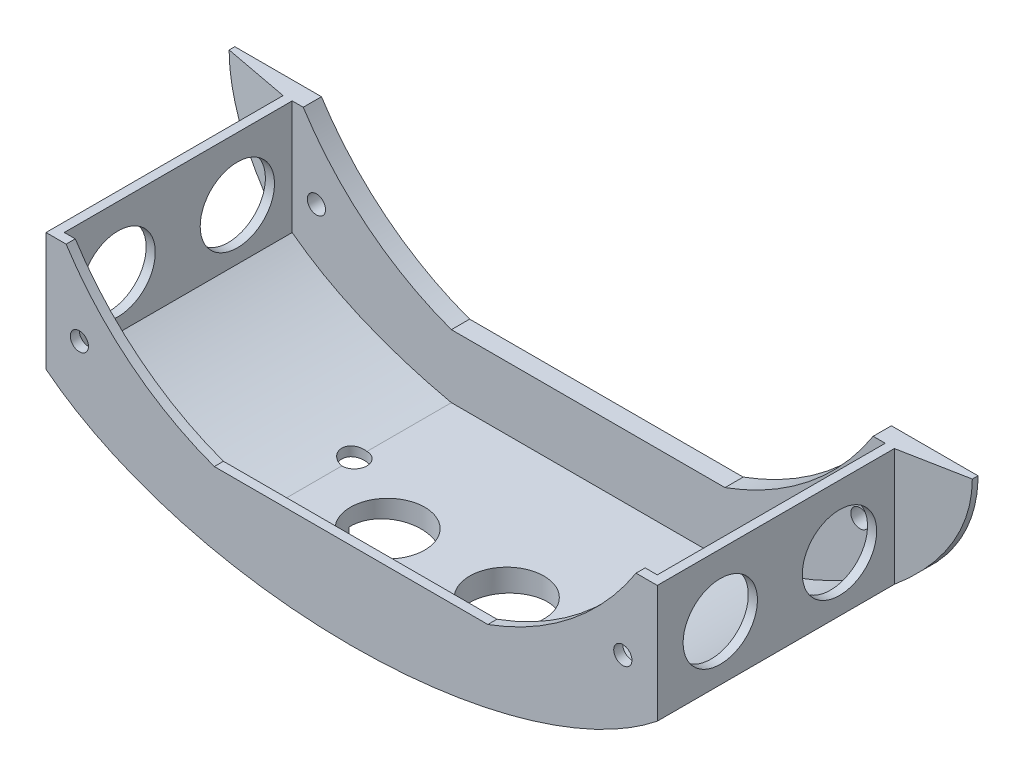
SolidWorks part; units mm, degrees
ref_plane "Alzado" through (0, 0, 0) normal (0, 0, 1) x (1, 0, 0)
ref_plane "Planta" through (0, 0, 0) normal (0, 1, 0) x (1, 0, 0)
ref_plane "Vista lateral" through (0, 0, 0) normal (1, 0, 0) x (0, 0, -1)
sketch "Croquis1" plane through (0, 0, 0) normal (0, 0, 1) x (1, 0, 0)
  line L0 (0, 14) -> (30, 14)
  line L1 (-76.5, 40) -> (-62.5, 40)
  line L2 (0, 14) -> (-30, 14)
  line L3 (0, 0) -> (0, 40) construction
  line L4 (62.5, 40) -> (76.5, 40)
  line L5 (-59.6, 23) -> (59.6, 23) construction
  line L6 (-7.25, 8) -> (7.25, 8) construction
  line L7 (81.5, 40) -> (76.5, 40)
  line L8 (-81.5, 40) -> (-76.5, 40)
  circle A1 centre (59.6, 23) radius 2
  circle A3 centre (-59.6, 23) radius 2
  arc A4 (-30, 14) -> (-62.5, 40) centre (-7.7821, 75.0849) cw
  arc A5 (30, 14) -> (62.5, 40) centre (7.7821, 75.0849) ccw
  ellipse E0 centre (0, 40) end of major axis (76.5, 40) minor radius 40 (-76.5, 40) -> (76.5, 40) ccw
  spline S0 degree 1 poles (-81.5, 40) (81.5, 40) knots 0 0 1 1 construction
  spline S1 degree 3 poles (-81.5, 40) (-81.5, 36.7505) (-80.261, 30.281) (-73.3217, 18.4428) (-57.7398, 6.4288) (-31.0655, -2.8514) (0, -6.0743) (31.0655, -2.8514) (57.7398, 6.4288) (73.3217, 18.4428) (80.261, 30.281) (81.5, 36.7505) (81.5, 40) knots 3.141593 3.141593 3.141593 3.141593 3.337942 3.534292 3.926991 4.31969 4.712389 5.105088 5.497787 5.890486 6.086836 6.283185 6.283185 6.283185 6.283185
  dimension "D3" = 65
  dimension "D4" = 4
  dimension "D1" = 153
  dimension "D2" = 30
  dimension "D5" = 40
  dimension "D6" = 14
  dimension "D7" = 14
  dimension "D8" = 119.2
  dimension "D9" = 15
  dimension "D10" = 8
  dimension "D11" = 14.5
  dimension "D12" = 5
extrude "Saliente-Extruir1" add sketch "Croquis1" along normal blind 4 contours L1 E0 L4 A5 L0 L2 A4 A1 A3 | L8 S1 L7 E0 region at (15, 12.4186, 0) region at (79, 38.309, 0)
sketch "Croquis3" plane through (0, 0, 4) normal (0, 0, 1) x (1, 0, 0)
  line L2 (-64.9152, 40) -> (-64.9152, 12.5008)
  line L4 (-81.5, 40) -> (-62.5, 40) construction
  line L6 (65.1546, 40) -> (65.1546, 12.6747)
  line L7 (62.5, 40) -> (81.5, 40) construction
  spline S1 degree 3 poles (1542.7355, -1097.7912) (170.097, 250.4745) (-119.0873, 96.5177) (-73.3217, 18.4428) (-57.7398, 6.4288) (-31.0655, -2.8514) (0, -6.0743) (31.0655, -2.8514) (57.7398, 6.4288) (73.3217, 18.4428) (119.0876, 96.5183) (-170.1018, 250.4771) (-1542.7713, -1097.8263) knots -1.252843 -1.252843 -1.252843 -1.252843 3.337942 3.534292 3.926991 4.31969 4.712389 5.105088 5.497787 5.890486 6.086836 10.67766 10.67766 10.67766 10.67766 only from (-81.5, 40) to (81.5, 40) construction
  spline S2 degree 3 poles (-81.5, 40) (-81.5, 36.7505) (-80.261, 30.281) (-73.3217, 18.4428) (-57.7398, 6.4288) (-31.0655, -2.8514) (0, -6.0743) (31.0655, -2.8514) (57.7398, 6.4288) (73.3217, 18.4428) (80.261, 30.281) (81.5, 36.7505) (81.5, 40) knots 3.141593 3.141593 3.141593 3.141593 3.337942 3.534292 3.926991 4.31969 4.712389 5.105088 5.497787 5.890486 6.086836 6.283185 6.283185 6.283185 6.283185
  spline S3 degree 1 poles (-79.5, 40) (79.5, 40) knots 0 0 1 1 construction
  spline S4 degree 3 poles (-79.5, 40) (-79.5, 36.9913) (-78.3621, 31.0317) (-73.4854, 22.677) (-65.8626, 15.2348) (-52.4779, 6.7299) (-30.655, -0.8785) (0, -4.0608) (30.655, -0.8785) (52.4779, 6.7299) (65.8626, 15.2348) (73.4854, 22.677) (78.3621, 31.0317) (79.5, 36.9913) (79.5, 40) knots 3.141593 3.141593 3.141593 3.141593 3.337942 3.534292 3.730641 3.926991 4.31969 4.712389 5.105088 5.497787 5.694137 5.890486 6.086836 6.283185 6.283185 6.283185 6.283185
  point P13 (62.5, 40)
  point P14 (64.5, 18.4921)
  point P25 (-66.5, 18.4921)
  point P29 (66.5, 18.4921)
  dimension "D1" = 2
extrude "Saliente-Extruir4" add sketch "Croquis3" along normal blind 50 contours S4 L2 S2 L6 region at (0.1522, -4.3162, 4)
sketch "Croquis4" plane through (0, 0, 4) normal (0, 0, 1) x (1, 0, 0)
  line L0 (-64.9152, 12.5008) -> (-64.9152, 40)
  line L1 (65.1546, 12.6747) -> (65.1546, 40)
  line L2 (62.5, 40) -> (65.1546, 40)
  line L3 (-81.5, 40) -> (-62.5, 40) construction
  line L4 (62.5, 40) -> (81.5, 40) construction
  line L5 (-64.9152, 14.9913) -> (-64.9152, 12.5008) construction
  line L6 (65.1546, 40) -> (67.1546, 40)
  line L7 (-62.5, 40) -> (-64.9152, 40)
  line L8 (67.1546, 40) -> (67.1546, 14.2025)
  line L9 (-64.9152, 40) -> (-66.9152, 40)
  line L10 (-66.9152, 40) -> (-66.9152, 14.0121)
  spline S0 degree 3 poles (2914.6022, -7.6993) (68.4607, 352.6912) (-191.4209, 55.1717) (-30.655, -0.8785) (0, -4.0608) (30.655, -0.8785) (191.4186, 55.1709) (-68.4528, 352.6821) (-2914.4643, -7.6818) knots -2.519994 -2.519994 -2.519994 -2.519994 3.926991 4.31969 4.712389 5.105088 5.497787 11.944668 11.944668 11.944668 11.944668 only from (-64.9152, 14.9913) to (65.1546, 15.1748) construction
  spline S1 degree 3 poles (-64.9152, 14.9913) (-62.1057, 12.8492) (-52.2108, 6.6368) (-30.655, -0.8785) (0, -4.0608) (30.655, -0.8785) (52.3277, 6.6776) (62.2857, 12.9624) (65.1546, 15.1748) knots 3.742654 3.742654 3.742654 3.742654 3.926991 4.31969 4.712389 5.105088 5.497787 5.687379 5.687379 5.687379 5.687379
  spline S2 degree 3 poles (2240.248, -1814.2238) (260.5568, 296.6585) (-125.1968, 106.9404) (-2.0113, -103.2111) (970.3665, 127.2722) (-2357.6152, 1836.2842) knots -1.944329 -1.944329 -1.944329 -1.944329 3.337942 3.534292 11.998045 11.998045 11.998045 11.998045 only from (-81.5, 40) to (-64.9152, 12.5008) construction
  spline S3 degree 3 poles (2357.9097, 1836.4354) (-970.4226, 127.2855) (2.0091, -103.2149) (125.1968, 106.9403) (-260.5566, 296.6583) (-2240.2462, -1814.2218) knots -2.573517 -2.573517 -2.573517 -2.573517 5.890486 6.086836 11.369105 11.369105 11.369105 11.369105 only from (65.1546, 12.6747) to (81.5, 40) construction
  spline S4 degree 3 poles (-81.5, 40) (-81.5, 36.7505) (-80.261, 30.281) (-74.7278, 20.8415) (-68.7218, 15.2513) (-64.9152, 12.5008) knots 3.141593 3.141593 3.141593 3.141593 3.337942 3.534292 3.767846 3.767846 3.767846 3.767846
  spline S5 degree 3 poles (65.1546, 12.6747) (68.8587, 15.3792) (74.7712, 20.9156) (80.261, 30.281) (81.5, 36.7505) (81.5, 40) knots 5.661843 5.661843 5.661843 5.661843 5.890486 6.086836 6.283185 6.283185 6.283185 6.283185
  line M39 (65.1546, 15.1748) -> (65.1546, 12.6747)
  spline M40 degree 3 poles (-81.5, 40) (-81.5, 36.7505) (-80.261, 30.281) (-73.3217, 18.4428) (-57.7398, 6.4288) (-31.0655, -2.8514) (0, -6.0743) (31.0655, -2.8514) (57.7398, 6.4288) (73.3217, 18.4428) (80.261, 30.281) (81.5, 36.7505) (81.5, 40) knots 3.141593 3.141593 3.141593 3.141593 3.337942 3.534292 3.926991 4.31969 4.712389 5.105088 5.497787 5.890486 6.086836 6.283185 6.283185 6.283185 6.283185 only from (65.1546, 12.6747) to (81.5, 40)
  line M41 (81.5, 40) -> (62.5, 40)
  line M45 (-62.5, 40) -> (-81.5, 40)
  spline M46 degree 3 poles (-81.5, 40) (-81.5, 36.7505) (-80.261, 30.281) (-73.3217, 18.4428) (-57.7398, 6.4288) (-31.0655, -2.8514) (0, -6.0743) (31.0655, -2.8514) (57.7398, 6.4288) (73.3217, 18.4428) (80.261, 30.281) (81.5, 36.7505) (81.5, 40) knots 3.141593 3.141593 3.141593 3.141593 3.337942 3.534292 3.926991 4.31969 4.712389 5.105088 5.497787 5.890486 6.086836 6.283185 6.283185 6.283185 6.283185 only from (-81.5, 40) to (-64.9152, 12.5008)
  line M47 (-64.9152, 12.5008) -> (-64.9152, 14.9913)
  dimension "D1" = 2
  dimension "D2" = 2
extrude "Saliente-Extruir5" add sketch "Croquis4" along normal blind 50 contours L8 L1 M41 M39 M40 | L10 L0 M45 M46 M47 region at (-65.9058, 26.619, 4) region at (66.145, 26.7099, 4)
ref_plane "Plano1" through (0, 40, 0) normal (0, 1, 0) x (1, 0, 0)
sketch "Croquis6" plane through (0, 0, 4) normal (0, 0, 1) x (1, 0, 0)
  line L0 (-30, 0.1323) -> (30, 0.1323)
  line L2 (-30, 14) -> (30, 14) construction
  spline S1 degree 3 poles (923.1346, 169.1134) (-49.932, 196.9469) (-146.0678, 39.3595) (-30.655, -0.8785) (0, -4.0608) (30.655, -0.8785) (146.0605, 39.357) (49.9451, 196.9254) (-922.918, 169.1196) knots -0.479691 -0.479691 -0.479691 -0.479691 3.926991 4.31969 4.712389 5.105088 5.497787 9.904142 9.904142 9.904142 9.904142 only from (-64.9152, 14.9913) to (65.1546, 15.1748) construction
  spline S2 degree 3 poles (-64.9152, 14.9913) (-62.1057, 12.8492) (-52.2108, 6.6368) (-30.655, -0.8785) (0, -4.0608) (30.655, -0.8785) (52.3277, 6.6776) (62.2857, 12.9624) (65.1546, 15.1748) knots 3.742654 3.742654 3.742654 3.742654 3.926991 4.31969 4.712389 5.105088 5.497787 5.687379 5.687379 5.687379 5.687379
  spline M21 degree 3 poles (-79.5, 40) (-79.5, 36.9913) (-78.3621, 31.0317) (-73.4854, 22.677) (-65.8626, 15.2348) (-52.4779, 6.7299) (-30.655, -0.8785) (0, -4.0608) (30.655, -0.8785) (52.4779, 6.7299) (65.8626, 15.2348) (73.4854, 22.677) (78.3621, 31.0317) (79.5, 36.9913) (79.5, 40) knots 3.141593 3.141593 3.141593 3.141593 3.337942 3.534292 3.730641 3.926991 4.31969 4.712389 5.105088 5.497787 5.694137 5.890486 6.086836 6.283185 6.283185 6.283185 6.283185 only from (-64.9152, 14.9913) to (65.1546, 15.1748)
extrude "Saliente-Extruir6" add sketch "Croquis6" along normal blind 50 contours L0 M21 region at (0, -1.1242, 4)
sketch "Croquis5" plane through (0, 40, 0) normal (0, 1, 0) x (-1, 0, 0)
  line L0 (-30, 25.2801) -> (30, 25.2801) construction
  line L2 (-13.075, 34.9209) -> (13.075, 34.9209) construction
  line L3 (0, 34.9209) -> (0, 25.2801) construction
  circle A0 centre (-13.075, 34.9209) radius 8.15
  circle A1 centre (13.075, 34.9209) radius 8.15
  circle A4 centre (-30, 25.2801) radius 2.75
  circle A5 centre (30, 25.2801) radius 2.75
  point P9 (0, 34.9209)
  dimension "D1" = 16.3
  dimension "D6" = 5.5
  dimension "D2" = 26.15
  dimension "D5" = 60
extrude "Cortar-Extruir1" cut sketch "Croquis5" against normal through all
sketch "Croquis7" plane through (-66.9152, 0, 0) normal (-1, 0, 0) x (0, 0, 1)
  line L0 (54, 26.2504) -> (4, 26.2504) construction
  circle A0 centre (42.1812, 26.2504) radius 8.15
  circle A1 centre (16.0312, 26.2504) radius 8.15
  dimension "D1" = 16.3
  dimension "D2" = 26.15
extrude "Cortar-Extruir2" cut sketch "Croquis7" against normal through all
sketch "Croquis8" plane through (0, 40, 0) normal (0, 1, 0) x (1, 0, 0)
  line L0 (67.1546, -4) -> (81.5, -1.245)
  line L4 (-66.9152, -4) -> (-81.5, -1.245)
  line L9 (81.5, -1.245) -> (81.5, -4)
  line L10 (81.5, -4) -> (67.1546, -4)
  line L11 (-66.9152, -4) -> (-81.5, -4)
  line L12 (-81.5, -4) -> (-81.5, -1.245)
  line L13 (-81.5, -4) -> (-81.5, 0) construction
  line L14 (81.5, -4) -> (81.5, 0) construction
  line L15 (81.5, -1.245) -> (-81.5, -1.245) construction
extrude "Cortar-Extruir3" cut sketch "Croquis8" against normal blind 45
ref_plane "Plano2" through (0, -6.8677, 0) normal (0, 1, 0) x (1, 0, 0)
sketch "Croquis9" plane through (0, -6.8677, 0) normal (0, 1, 0) x (1, 0, 0)
  line L0 (20.3221, -43.9567) -> (14.6354, -48.0385) construction
  line L1 (20.9053, -44.7691) -> (15.2185, -48.8509)
  line L2 (19.739, -43.1443) -> (14.0523, -47.2261)
  line L3 (-14.6354, -48.0385) -> (-20.3221, -43.9567) construction
  line L4 (-15.2185, -48.8509) -> (-20.9053, -44.7691)
  line L5 (-14.0523, -47.2261) -> (-19.739, -43.1443)
  line L6 (0, -75.4431) -> (0, -13.0226) construction
  line L7 (14.6354, -48.0385) -> (-14.6354, -48.0385) construction
  line L8 (20.3221, -43.9567) -> (-20.3221, -43.9567) construction
  arc A0 (20.9053, -44.7691) -> (19.739, -43.1443) centre (20.3221, -43.9567) ccw
  arc A1 (14.0523, -47.2261) -> (15.2185, -48.8509) centre (14.6354, -48.0385) ccw
  arc A2 (-15.2185, -48.8509) -> (-14.0523, -47.2261) centre (-14.6354, -48.0385) ccw
  arc A3 (-19.739, -43.1443) -> (-20.9053, -44.7691) centre (-20.3221, -43.9567) ccw
  arc A4 (20.8514, -37.36) -> (21.2203, -35.1975) centre (13.075, -34.9209) ccw
  arc A5 (10.6701, -23.7055) -> (-11.3066, -23.7055) centre (-0.3183, -51.6157) ccw
  arc A6 (11.0364, -22.7751) -> (-11.673, -22.7751) centre (-0.3183, -51.6157) ccw
  arc A7 (10.6701, -23.7055) -> (11.0364, -22.7751) centre (10.8532, -23.2403) ccw
  arc A8 (-11.673, -22.7751) -> (-11.3066, -23.7055) centre (-11.4898, -23.2403) ccw
  arc A9 (-20.8514, -37.36) -> (-21.2203, -35.1975) centre (-13.075, -34.9209) cw
  circle A10 centre (13.075, -34.9209) radius 8.15 construction
  circle A11 centre (-13.075, -34.9209) radius 8.15 construction
  ellipse E0 centre (0, -26.7771) end of major axis (-3.84, -26.794) minor radius 1.3066
  spline S0 degree 3 poles (20.8514, -37.36) (21.718, -37.7759) (22.9802, -38.3348) (22.8701, -38.1249) (25.1741, -40.2651) knots 0 0 0 0 0.283617 1 1 1 1
  spline S1 degree 3 poles (25.1741, -40.2651) (24.4976, -36.3849) (23.9569, -35.7927) (21.2203, -35.1975) knots 0 0 0 0 0.707855 0.707855 0.707855 0.707855
  spline S2 degree 3 poles (-25.1741, -40.2651) (-24.4976, -36.3849) (-23.9569, -35.7927) (-21.2203, -35.1975) knots 0 0 0 0 0.707855 0.707855 0.707855 0.707855
  spline S3 degree 3 poles (-20.8514, -37.36) (-21.718, -37.7759) (-22.9802, -38.3348) (-22.8701, -38.1249) (-25.1741, -40.2651) knots 0 0 0 0 0.283617 1 1 1 1
  point P2 (17.4788, -45.9976)
  point P7 (-17.4788, -45.9976)
  point P46 (0, -43.9567)
  dimension "D2" = 1
  dimension "D1" = 7
extrude "Saliente-Extruir7" add sketch "Croquis9" along normal up to next
sketch "Croquis10" plane through (0, 0, 54) normal (0, 0, 1) x (1, 0, 0)
  line L1 (-66.9152, 40) -> (-66.9152, 14.0121)
  line L2 (-30, 14) -> (30, 14) construction
  line L3 (-30, 14) -> (30, 14)
  line L5 (-62.5, 40) -> (-66.9152, 40)
  line L8 (67.1546, 40) -> (67.1546, 14.2025)
  line L9 (67.1546, 40) -> (62.5, 40)
  line L11 (-66.9152, 40) -> (-66.9152, 14.0121) construction
  line L12 (-66.9152, 40) -> (-81.5, 40) construction
  arc A0 (-62.5, 40) -> (-30, 14) centre (-7.7821, 75.0849) ccw construction
  arc A1 (30, 14) -> (62.5, 40) centre (7.7821, 75.0849) ccw construction
  arc A2 (-62.5, 40) -> (-30, 14) centre (-7.7821, 75.0849) ccw
  arc A3 (30, 14) -> (62.5, 40) centre (7.7821, 75.0849) ccw
  circle A4 centre (59.6, 23) radius 2 construction
  circle A5 centre (-59.6, 23) radius 2 construction
  circle A6 centre (59.6, 23) radius 2
  circle A7 centre (-59.6, 23) radius 2
  spline S0 degree 3 poles (1888.9331, 367.4807) (-3.4105, 291.6772) (-174.9969, 47.2237) (-31.0655, -2.8514) (0, -6.0743) (31.0655, -2.8514) (174.9926, 47.2222) (3.4214, 291.6617) (-1888.7409, 367.473) knots -1.644502 -1.644502 -1.644502 -1.644502 3.926991 4.31969 4.712389 5.105088 5.497787 11.069092 11.069092 11.069092 11.069092 only from (-66.9152, 14.0121) to (67.1546, 14.2025) construction
  spline S1 degree 3 poles (-66.9152, 14.0121) (-63.8083, 11.5553) (-53.4025, 4.9198) (-31.0655, -2.8514) (0, -6.0743) (31.0655, -2.8514) (53.5199, 4.9606) (63.9898, 11.6713) (67.1546, 14.2025) knots 3.725851 3.725851 3.725851 3.725851 3.926991 4.31969 4.712389 5.105088 5.497787 5.704111 5.704111 5.704111 5.704111
extrude "Saliente-Extruir8" add sketch "Croquis10" along normal blind 2
